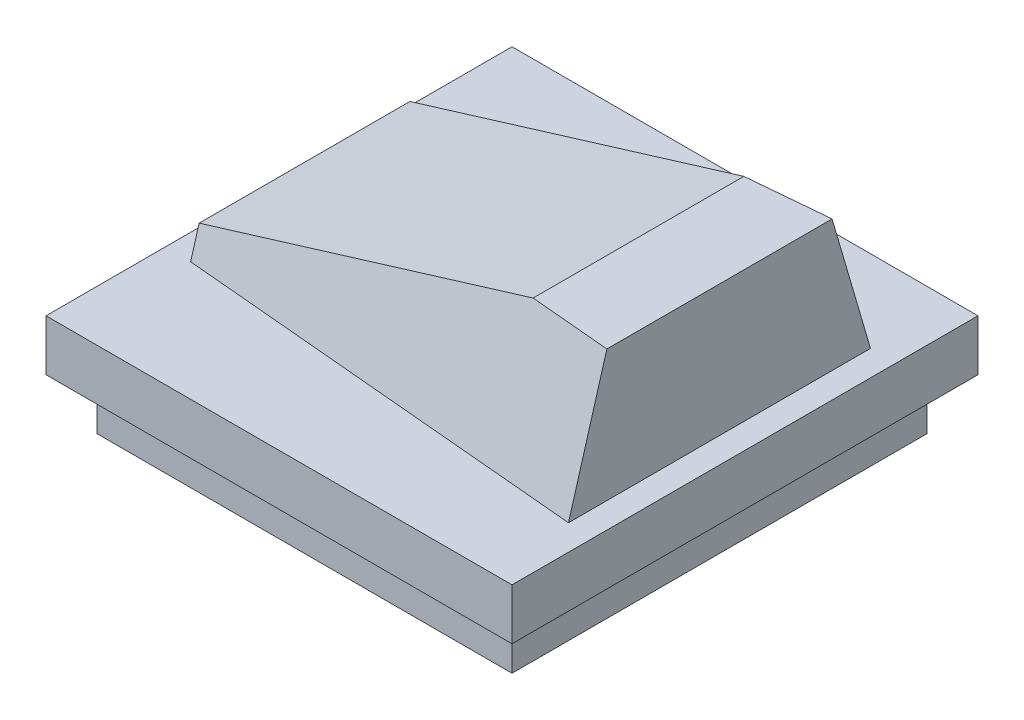
SolidWorks part; units mm, degrees
ref_plane "Front Plane" through (0, 0, 0) normal (0, 0, 1) x (1, 0, 0)
ref_plane "Top Plane" through (0, 0, 0) normal (0, 1, 0) x (1, 0, 0)
ref_plane "Right Plane" through (0, 0, 0) normal (1, 0, 0) x (0, 0, -1)
sketch "Sketch2" plane through (0, 0, 0) normal (0, 1, 0) x (1, 0, 0)
  line L1 (0, 0) -> (812.8, 0)
  line L2 (0, 0) -> (0, 812.8)
  line L3 (0, 812.8) -> (812.8, 812.8)
  line L4 (812.8, 0) -> (812.8, 812.8)
  dimension "D1" = 812.8
  dimension "D2" = 812.8
extrude "Boss-Extrude1" add sketch "Sketch2" along normal blind 457.2
ref_plane "Plane1" through (0, 100, 0) normal (0, 1, 0) x (1, 0, 0)
sketch "Sketch3" plane through (0, 100, 0) normal (0, 1, 0) x (1, 0, 0)
  line L1 (-50, -50) -> (862.8, -50)
  line L2 (-50, -50) -> (-50, 862.8)
  line L3 (-50, 862.8) -> (862.8, 862.8)
  line L4 (862.8, -50) -> (862.8, 862.8)
  line L6 (0, 0) -> (812.8, 0)
  line L7 (0, 0) -> (0, 812.8)
  line L8 (0, 812.8) -> (812.8, 812.8)
  line L9 (812.8, 0) -> (812.8, 812.8)
  point P11 (857.8797, 879.0425)
  dimension "D1" = 812.8
  dimension "D2" = 812.8
  dimension "D3" = 50
  dimension "D4" = 50
  dimension "D5" = 50
  dimension "D6" = 50
extrude "Boss-Extrude2" add sketch "Sketch3" along normal blind 100
chamfer "Chamfer4" distance 200 angle 73 1 edges at (0, 457.2, -406.4) first distance on face at (0, 328.6, -406.4)
chamfer "Chamfer5" distance 200 angle 73 2 edges at (327.0853, 357.2, -812.8) (327.0853, 357.2, 0) first distance on face at (327.0853, 357.2, -406.4)
